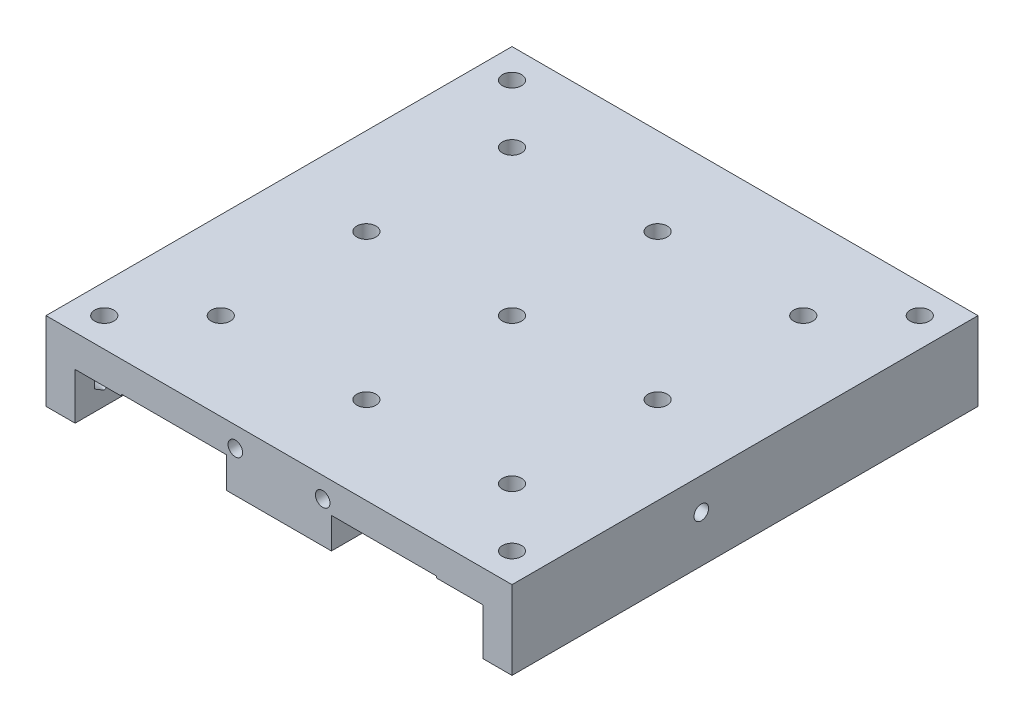
SolidWorks part; units mm, degrees
material "6061"
ref_plane "前视" through (0, 0, 0) normal (0, 0, 1) x (1, 0, 0)
ref_plane "上视" through (0, 0, 0) normal (0, 1, 0) x (1, 0, 0)
ref_plane "右视" through (0, 0, 0) normal (1, 0, 0) x (0, 0, -1)
sketch "草图1" plane through (0, 0, 0) normal (0, 1, 0) x (1, 0, 0)
  line L1 (-40, -40) -> (40, -40)
  line L2 (-40, -40) -> (-40, 40)
  line L3 (-40, 40) -> (40, 40)
  line L4 (40, -40) -> (40, 40)
  line L5 (-40, -40) -> (40, 40) construction
  line L6 (-40, 40) -> (40, -40) construction
  point P0 (0, 0)
  dimension "D1" = 80
extrude "凸台-拉伸1" add sketch "草图1" along normal blind 13.5
sketch "草图2" plane through (0, 0, 40) normal (0, 0, 1) x (1, 0, 0)
  line L0 (0, 0) -> (0, 17.1926) construction
  line L1 (-40, 0) -> (40, 0) construction
  line L2 (-35, 3) -> (35, 3)
  line L3 (-35, 3) -> (-35, 0)
  line L4 (-35, 0) -> (35, 0)
  line L5 (35, 3) -> (35, 0)
  line L6 (-35, 3) -> (35, 0) construction
  line L7 (-35, 0) -> (35, 3) construction
  point P3 (0, 1.5)
  dimension "D1" = 70
  dimension "D2" = 3
extrude "切除-拉伸1" cut sketch "草图2" against normal through all
sketch "草图11" plane through (0, 0, 40) normal (0, 0, 1) x (1, 0, 0)
  line L0 (35, 3) -> (-35, 3) construction
  line L1 (-35, 3) -> (-9, 3)
  line L2 (-35, 3) -> (-35, 8)
  line L3 (-35, 8) -> (-9, 8)
  line L4 (-9, 3) -> (-9, 8)
  line L5 (0, 3) -> (0, 22.3011) construction
  line L6 (9, 3) -> (9, 8)
  line L7 (35, 8) -> (9, 8)
  line L8 (35, 3) -> (35, 8)
  line L9 (35, 3) -> (9, 3)
  dimension "D1" = 5
  dimension "D2" = 18
extrude "切除-拉伸2" cut sketch "草图11" against normal through all
sketch "草图12" plane through (0, 0, 40) normal (0, 0, 1) x (1, 0, 0)
  line L0 (0, 3) -> (0, 22.8989) construction
  line L1 (9, 3) -> (-9, 3) construction
  line L2 (27, 8) -> (27, 8.3)
  line L3 (-9, 8) -> (-27, 8)
  line L4 (-9, 8) -> (-9, 8.3)
  line L5 (-9, 8.3) -> (-27, 8.3)
  line L6 (-27, 8) -> (-27, 8.3)
  line L7 (9, 8.3) -> (27, 8.3)
  line L8 (9, 8) -> (9, 8.3)
  line L9 (9, 8) -> (27, 8)
  dimension "D1" = 0.3
  dimension "D2" = 54
extrude "切除-拉伸3" cut sketch "草图12" against normal through all
hole_wizard "M3 螺纹孔1" positions "草图4" profile "草图3" tap size "M3" standard "Gb"
sketch "草图4" plane through (40, 0, 0) normal (1, 0, 0) x (0, 0, -1)
  line L0 (-40, 13.5) -> (40, 13.5) construction
  line L2 (40, 13.5) -> (40, 0) construction
  point P0 (-7.5, 8)
  dimension "D1" = 5.5
  dimension "D2" = 47.5
sketch "草图3" plane through (40, 8, 7.5) normal (0, 1, 0) x (0, 0, -1)
  line L0 (0, 0) -> (0, 8.2511)
  line L1 (0, 8.2511) -> (1.25, 7.5)
  line L2 (1.25, 7.5) -> (1.25, 0)
  line L5 (1.25, 0) -> (0, 0)
  line L10 (0, 8.2511) -> (-1.25, 7.5) construction
  line L11 (0, -6.35) -> (0, 107.95) construction
  dimension "螺纹孔钻头直径" = 2.5
  dimension "螺纹孔钻头深度" = 7.5
  dimension "导头角度" = 118
cosmetic thread "孔螺蚊线1" parameters "D1"=6, "D2"=3
hole_wizard "M4 螺纹孔1" positions "草图6" profile "草图5" tap size "M4" standard "Gb"
sketch "草图6" plane through (0, 13.5, 0) normal (0, 1, 0) x (1, 0, 0)
  line L0 (0, 40) -> (0, 0) construction
  line L1 (40, 40) -> (-40, 40) construction
  line L2 (0, 0) -> (-40, 0) construction
  line L3 (-40, 40) -> (-40, -40) construction
  point P0 (-25, -25)
  dimension "D1" = 50
  dimension "D2" = 50
sketch "草图5" plane through (-25, 13.5, 25) normal (1, 0, 0) x (0, 0, 1)
  line L0 (0, 0) -> (0, 11.0914)
  line L1 (0, 11.0914) -> (1.65, 10.1)
  line L2 (1.65, 10.1) -> (1.65, 0)
  line L5 (1.65, 0) -> (0, 0)
  line L10 (0, 11.0914) -> (-1.65, 10.1) construction
  line L11 (0, -6.35) -> (0, 107.95) construction
  dimension "螺纹孔钻头直径" = 3.3
  dimension "螺纹孔钻头深度" = 10.1
  dimension "导头角度" = 118
cosmetic thread "孔螺蚊线2" parameters "D1"=8, "D2"=4
pattern_linear "阵列(线性)2" count 3 spacing 25 along (1, 0, 0) count 3 spacing 25 along (0, 0, -1) of "M4 螺纹孔1"
hole_wizard "M3 螺纹孔2" positions "草图8" profile "草图7" tap size "M3" standard "Gb"
sketch "草图8" plane through (-40, 0, 0) normal (-1, 0, 0) x (0, 0, 1)
  line L0 (40, 13.5) -> (40, 0) construction
  line L1 (-40, 13.5) -> (40, 13.5) construction
  point P0 (7, 9.5)
  point P2 (-13, 9.5)
  dimension "D1" = 33
  dimension "D2" = 20
  dimension "D3" = 4
sketch "草图7" plane through (-40, 9.5, 7) normal (0, 1, 0) x (0, 0, 1)
  line L0 (0, 0) -> (0, 8.2511)
  line L1 (0, 8.2511) -> (1.25, 7.5)
  line L2 (1.25, 7.5) -> (1.25, 0)
  line L5 (1.25, 0) -> (0, 0)
  line L10 (0, 8.2511) -> (-1.25, 7.5) construction
  line L11 (0, -6.35) -> (0, 107.95) construction
  dimension "螺纹孔钻头直径" = 2.5
  dimension "螺纹孔钻头深度" = 7.5
  dimension "导头角度" = 118
cosmetic thread "孔螺蚊线4" parameters "D1"=6, "D2"=3
cosmetic thread "孔螺蚊线9" parameters "D1"=6, "D2"=3
hole_wizard "M4 螺纹孔2" positions "草图10" profile "草图9" tap size "M4" standard "Gb"
sketch "草图10" plane through (0, 13.5, 0) normal (0, 1, 0) x (1, 0, 0)
  line L0 (0, 40) -> (0, 0) construction
  line L1 (40, 40) -> (-40, 40) construction
  line L2 (0, 0) -> (40, 0) construction
  line L3 (40, -40) -> (40, 40) construction
  point P0 (-35, 35)
  point P14 (35, 35)
  point P15 (35, -35)
  point P16 (-35, -35)
  dimension "D1" = 70
  dimension "D2" = 70
sketch "草图9" plane through (-35, 13.5, -35) normal (1, 0, 0) x (0, 0, 1)
  line L0 (0, 0) -> (0, 11.0914)
  line L1 (0, 11.0914) -> (1.65, 10.1)
  line L2 (1.65, 10.1) -> (1.65, 0)
  line L5 (1.65, 0) -> (0, 0)
  line L10 (0, 11.0914) -> (-1.65, 10.1) construction
  line L11 (0, -6.35) -> (0, 107.95) construction
  dimension "螺纹孔钻头直径" = 3.3
  dimension "螺纹孔钻头深度" = 10.1
  dimension "导头角度" = 118
cosmetic thread "孔螺蚊线5" parameters "D1"=8, "D2"=4
cosmetic thread "孔螺蚊线6" parameters "D1"=8, "D2"=4
cosmetic thread "孔螺蚊线7" parameters "D1"=8, "D2"=4
cosmetic thread "孔螺蚊线8" parameters "D1"=8, "D2"=4
hole_wizard "M3 螺纹孔3" positions "草图14" profile "草图13" tap size "M3" standard "Gb"
sketch "草图14" plane through (0, 0, 40) normal (0, 0, 1) x (1, 0, 0)
  line L0 (0, 13.5) -> (0, -1.6092) construction
  line L1 (-40, 13.5) -> (40, 13.5) construction
  point P0 (-7.5, 10)
  point P11 (7.5, 10)
  dimension "D1" = 15
  dimension "D2" = 3.5
sketch "草图13" plane through (-7.5, 10, 40) normal (1, 0, 0) x (0, -1, 0)
  line L0 (0, 0) -> (0, 8.2511)
  line L1 (0, 8.2511) -> (1.25, 7.5)
  line L2 (1.25, 7.5) -> (1.25, 0)
  line L5 (1.25, 0) -> (0, 0)
  line L10 (0, 8.2511) -> (-1.25, 7.5) construction
  line L11 (0, -6.35) -> (0, 107.95) construction
  dimension "螺纹孔钻头直径" = 2.5
  dimension "螺纹孔钻头深度" = 7.5
  dimension "导头角度" = 118
cosmetic thread "孔螺蚊线10" parameters "D1"=6, "D2"=3
cosmetic thread "孔螺蚊线11" parameters "D1"=6, "D2"=3
mirror "镜向1" about plane through (0, 0, 0) normal (0, 0, 1) of "M3 螺纹孔3"
